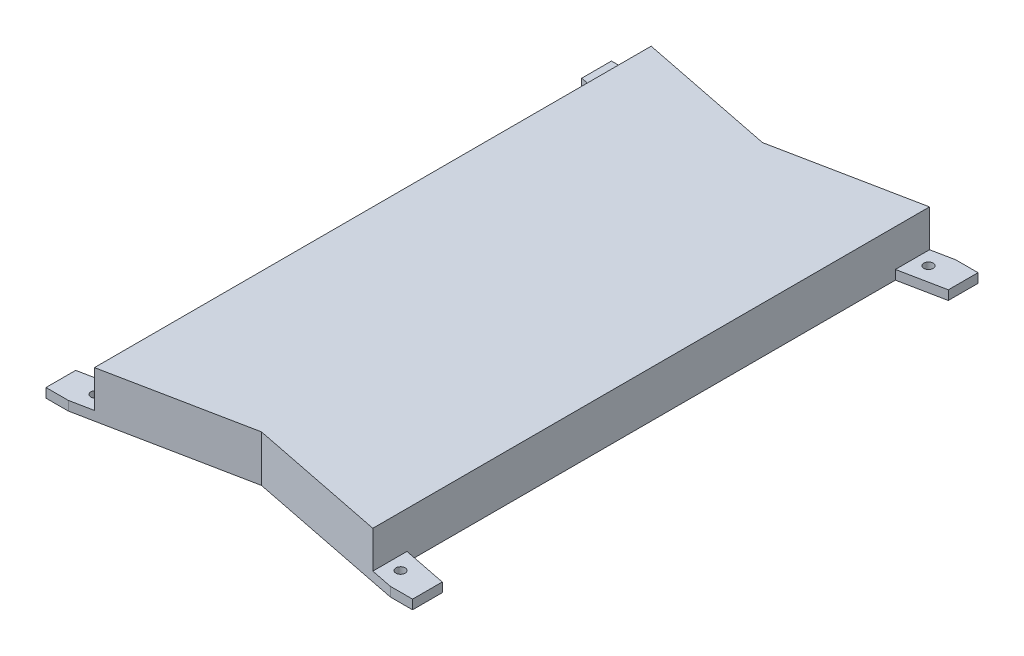
SolidWorks part; units mm, degrees
ref_plane "Front Plane" through (0, 0, 0) normal (0, 0, 1) x (1, 0, 0)
ref_plane "Top Plane" through (0, 0, 0) normal (0, 1, 0) x (1, 0, 0)
ref_plane "Right Plane" through (0, 0, 0) normal (1, 0, 0) x (0, 0, -1)
ref_axis "X" through (-88.99, 0, 0) along (1, 0, 0)
ref_axis "Y" through (0, 55, 0) along (0, -1, 0)
ref_axis "Z" through (0, 0, -88.99) along (0, 0, 1)
sketch "Sketch1" plane through (0, 0, 0) normal (0, 1, 0) x (1, 0, 0)
  line L0 (-75, 131.6) -> (-75, -131.6)
  line L1 (-75, -150) -> (0, -135)
  line L2 (0, -135) -> (75, -150)
  line L3 (75, -131.6) -> (75, 131.6)
  line L4 (75, 150) -> (0, 135)
  line L5 (0, 135) -> (-75, 150)
  line L6 (0, 135) -> (0, -135) construction
  line L7 (-75, 0) -> (75, 0) construction
  line L8 (75, -150) -> (86.767, -152.3534)
  line L9 (86.767, -152.3534) -> (98.767, -152.3534)
  line L10 (98.767, -152.3534) -> (98.767, -136.3534)
  line L11 (98.767, -136.3534) -> (75, -131.6)
  line L12 (98.767, 136.3534) -> (75, 131.6)
  line L13 (98.767, 152.3534) -> (98.767, 136.3534)
  line L14 (86.767, 152.3534) -> (98.767, 152.3534)
  line L15 (75, 150) -> (86.767, 152.3534)
  line L16 (-98.767, -152.3534) -> (-98.767, -136.3534)
  line L17 (-86.767, -152.3534) -> (-98.767, -152.3534)
  line L18 (-75, -150) -> (-86.767, -152.3534)
  line L19 (-98.767, -136.3534) -> (-75, -131.6)
  line L20 (-98.767, 136.3534) -> (-75, 131.6)
  line L21 (-98.767, 152.3534) -> (-98.767, 136.3534)
  line L22 (-86.767, 152.3534) -> (-98.767, 152.3534)
  line L23 (-75, 150) -> (-86.767, 152.3534)
  line L24 (-75, 150) -> (-75, 131.6) construction
  line L25 (75, 150) -> (75, 131.6) construction
  line L26 (75, -131.6) -> (75, -150) construction
  line L27 (-75, -131.6) -> (-75, -150) construction
  dimension "D1" = 300
  dimension "D2" = 270
  dimension "D3" = 150
  dimension "D4" = 12
  dimension "D5" = 16
  dimension "D6" = 12
extrude "Boss-Extrude1" add sketch "Sketch1" along normal blind 5
sketch "Sketch3" plane through (0, 5, 0) normal (0, 1, 0) x (1, 0, 0)
  line L0 (-75, 131.6) -> (-75, 150) construction
  line L1 (0, 135) -> (-86.767, 152.3534) construction
  line L2 (75, 131.6) -> (75, 150) construction
  line L3 (86.767, 152.3534) -> (0, 135) construction
  line L4 (-75, -131.6) -> (-75, -150) construction
  line L5 (-86.767, -152.3534) -> (0, -135) construction
  line L6 (75, -131.6) -> (75, -150) construction
  line L7 (0, -135) -> (86.767, -152.3534) construction
  line L8 (-75, 131.6) -> (-75, -131.6) construction
  line L9 (75, -131.6) -> (75, 131.6) construction
  line L10 (75, 150) -> (0, 135)
  line L11 (0, 135) -> (-75, 150)
  line L12 (75, -131.6) -> (75, 131.6)
  line L13 (0, -135) -> (75, -150)
  line L14 (-75, 131.6) -> (-75, -131.6)
  line L15 (-75, -150) -> (0, -135)
  line L16 (-73, -147.5604) -> (0, -132.9604)
  line L17 (0, -132.9604) -> (73, -147.5604)
  line L18 (73, -131.6) -> (73, -147.5604)
  line L19 (73, -131.6) -> (73, 131.6)
  line L20 (73, 131.6) -> (73, 147.5604)
  line L21 (73, 147.5604) -> (0, 132.9604)
  line L22 (0, 132.9604) -> (-73, 147.5604)
  line L23 (-73, 131.6) -> (-73, 147.5604)
  line L24 (-73, 131.6) -> (-73, -131.6)
  line L25 (-73, -131.6) -> (-73, -147.5604)
  line L26 (75, 0) -> (-75, 0) construction
  line L27 (0, -135) -> (0, 135) construction
  line L28 (80.4076, -151.0815) -> (83.9461, -133.3892) construction
  line L29 (98.767, -136.3534) -> (75, -131.6) construction
  circle A0 centre (82.1768, -142.2354) radius 2.5
  circle A1 centre (-82.1768, -142.2354) radius 2.5
  circle A2 centre (-82.1768, 142.2354) radius 2.5
  circle A3 centre (82.1768, 142.2354) radius 2.5
  dimension "D2" = 5
  dimension "D3" = 82
  dimension "D1" = 2
extrude "Cut-Extrude1" cut sketch "Sketch3" against normal through all contours L24 L25 L16 L17 L18 L19 L20 L21 L22 L23 | A1 | A0 | A2 | A3 region at (0, 5, 0) region at (82.1768, 5, 142.2354) region at (-82.1768, 5, 142.2354) region at (-82.1768, 5, -142.2354) region at (82.1768, 5, -142.2354)
sketch "Sketch4" plane through (0, 5, 0) normal (0, 1, 0) x (1, 0, 0)
  line L0 (0, -132.9604) -> (73, -147.5604) construction
  line L1 (-73, -147.5604) -> (0, -132.9604) construction
  line L2 (73, 147.5604) -> (73, -147.5604) construction
  line L3 (73, 147.5604) -> (0, 132.9604) construction
  line L4 (0, 132.9604) -> (-73, 147.5604) construction
  line L5 (-73, 147.5604) -> (-73, -147.5604) construction
  line L6 (0, -132.9604) -> (73, -147.5604)
  line L7 (-73, -147.5604) -> (0, -132.9604)
  line L8 (73, 147.5604) -> (73, -147.5604)
  line L9 (73, 147.5604) -> (0, 132.9604)
  line L10 (0, 132.9604) -> (-73, 147.5604)
  line L11 (-73, 147.5604) -> (-73, -147.5604)
  line L12 (-75, 150) -> (-75, -150)
  line L13 (-75, -150) -> (0, -135)
  line L14 (0, -135) -> (75, -150)
  line L15 (75, 150) -> (75, -150)
  line L16 (75, 150) -> (0, 135)
  line L17 (0, 135) -> (-75, 150)
  dimension "D1" = 2
extrude "Boss-Extrude2" add sketch "Sketch4" along normal blind 20
sketch "Sketch5" plane through (0, 25, 0) normal (0, 1, 0) x (1, 0, 0)
  line L0 (75, 150) -> (0, 135) construction
  line L1 (0, 135) -> (-75, 150) construction
  line L2 (-75, 150) -> (-75, -150) construction
  line L3 (-75, -150) -> (0, -135) construction
  line L4 (0, -135) -> (75, -150) construction
  line L5 (75, -150) -> (75, 150) construction
  line L6 (75, 150) -> (0, 135)
  line L7 (0, 135) -> (-75, 150)
  line L8 (-75, 150) -> (-75, -150)
  line L9 (-75, -150) -> (0, -135)
  line L10 (0, -135) -> (75, -150)
  line L11 (75, -150) -> (75, 150)
extrude "Boss-Extrude3" add sketch "Sketch5" against normal blind 5
